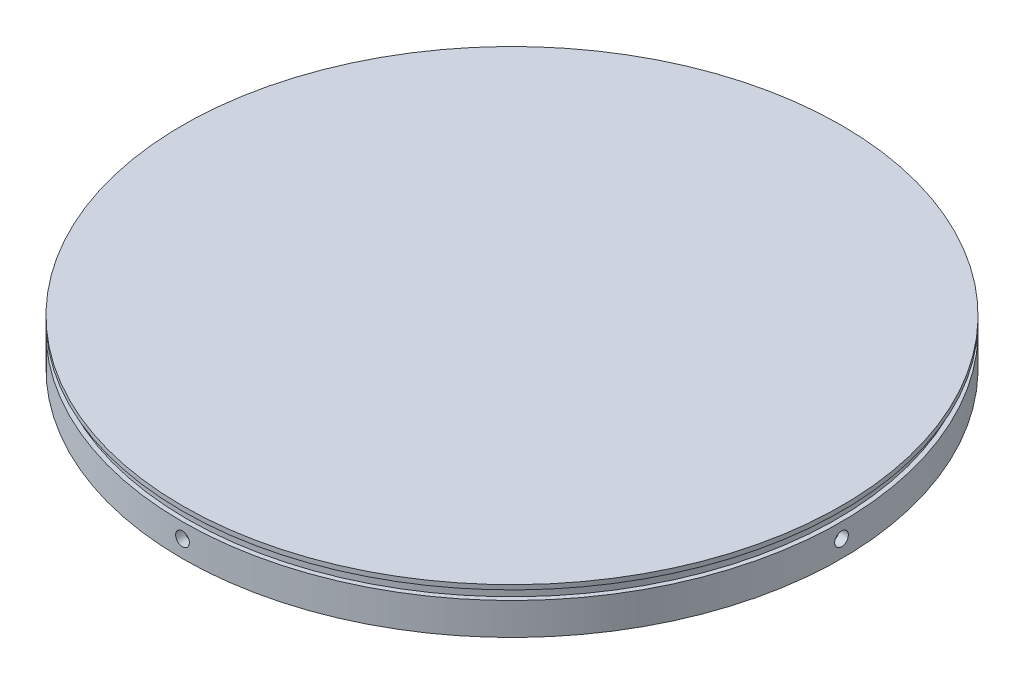
SolidWorks part; units mm, degrees
ref_plane "前基準面" through (0, 0, 0) normal (0, 0, 1) x (1, 0, 0)
ref_plane "上基準面" through (0, 0, 0) normal (0, 1, 0) x (1, 0, 0)
ref_plane "右基準面" through (0, 0, 0) normal (1, 0, 0) x (0, 0, -1)
sketch "草圖9" plane through (0, 0, 0) normal (0, 1, 0) x (1, 0, 0)
  line L0 (0, 0) -> (0, 76.3417) construction
  circle A0 centre (0, 0) radius 66
  circle A1 centre (0, 0) radius 70
  circle A2 centre (0, 0) radius 72
  point P5 (0, 72)
  dimension "D1" = 2
  dimension "D2" = 4
  dimension "D3" = 144
extrude "填料-伸長9" add sketch "草圖9" against normal blind 10 contours A2 A1 region at (-71.7964, 0, 0)
extrude "填料-伸長10" add sketch "草圖9<18>" against normal blind 2.5 contours A1 A0 region at (-68.0201, 0, 0)
sketch "草圖9<18>" plane through (0, 0, 0) normal (0, 1, 0) x (1, 0, 0) same geometry as "草圖9"
extrude "填料-伸長11" add sketch "草圖9<19>" against normal blind 10 contours A0 region at (0, 0, 0)
sketch "草圖9<19>" plane through (0, 0, 0) normal (0, 1, 0) x (1, 0, 0) same geometry as "草圖9"
shell "薄殼2" thickness 2 removed face at (0, -10, 66)
sketch "草圖10" plane through (0, 0, 0) normal (0, 1, 0) x (1, 0, 0)
  circle A0 centre (-54.1329, 0) radius 1.5828
sketch "草圖11" plane through (0, 0, 0) normal (0, 1, 0) x (1, 0, 0)
  line L1 (-34, 34) -> (34, 34)
  line L2 (-34, 34) -> (-34, -34)
  line L3 (-34, -34) -> (34, -34)
  line L4 (34, 34) -> (34, -34)
  line L5 (-34, 34) -> (34, -34) construction
  line L6 (-34, -34) -> (34, 34) construction
  point P0 (0, 0)
  point P7 (-30, 30)
  point P10 (30, 30)
  point P11 (30, -30)
  point P12 (-30, -30)
  point P13 (0, 0)
  dimension "D1" = 68
  dimension "D2" = 4
  dimension "D3" = 4
sketch "草圖13" plane through (0, 0, 0) normal (0, 0, 1) x (1, 0, 0)
  line L0 (0, 0) -> (0, -10) construction
  line L1 (-72, -10) -> (72, -10) construction
  point P5 (0, -6.25)
  dimension "D1" = 3.75
hole_wizard "Ø3.0mm 定位孔1" positions "3D草圖2" profile "草圖14" hole size "Ø3.0" standard "JIS" end condition up to next
sketch3d "3D草圖2"
  point P0 (0, -6.25, 72)
sketch "草圖14" plane through (0, -6.25, 72) normal (1, 0, 0) x (0, -1, 0)
  line L0 (0, 0) -> (0, 8)
  line L1 (0, 8) -> (1.5, 8)
  line L2 (1.5, 8) -> (1.5, 0)
  line L5 (1.5, 0) -> (0, 0)
  line L11 (0, -6.35) -> (0, 107.95) construction
  dimension "貫穿孔直徑" = 3
  dimension "貫穿孔深度" = 8
pattern_circular "環狀複製排列1" count 4 over 360 about axis through (0, -10, 0) along (0, 1, 0) of "Ø3.0mm 定位孔1"
ref_plane "平面1" through (0, 0, 0) normal (1, 0, 0) x (0, 0, -1)
sketch "草圖15" plane through (0, 0, 0) normal (1, 0, 0) x (0, 0, -1)
  line L0 (-72, 0) -> (-72, -4.75) construction
  line L1 (-72, -1) -> (-71, -1)
  line L2 (-72, -1) -> (-72, -3)
  line L3 (-72, -3) -> (-71, -3)
  line L4 (-71, -1) -> (-71, -3)
  line L5 (-72, -1) -> (-71, -3) construction
  line L6 (-72, -3) -> (-71, -1) construction
  line L7 (72, 0) -> (-72, 0) construction
  point P0 (-71.5, -2)
  dimension "D1" = 1
  dimension "D2" = 2
  dimension "D3" = 1
revolve "除料-旋轉2" cut sketch "草圖15" angle 360 about L0
